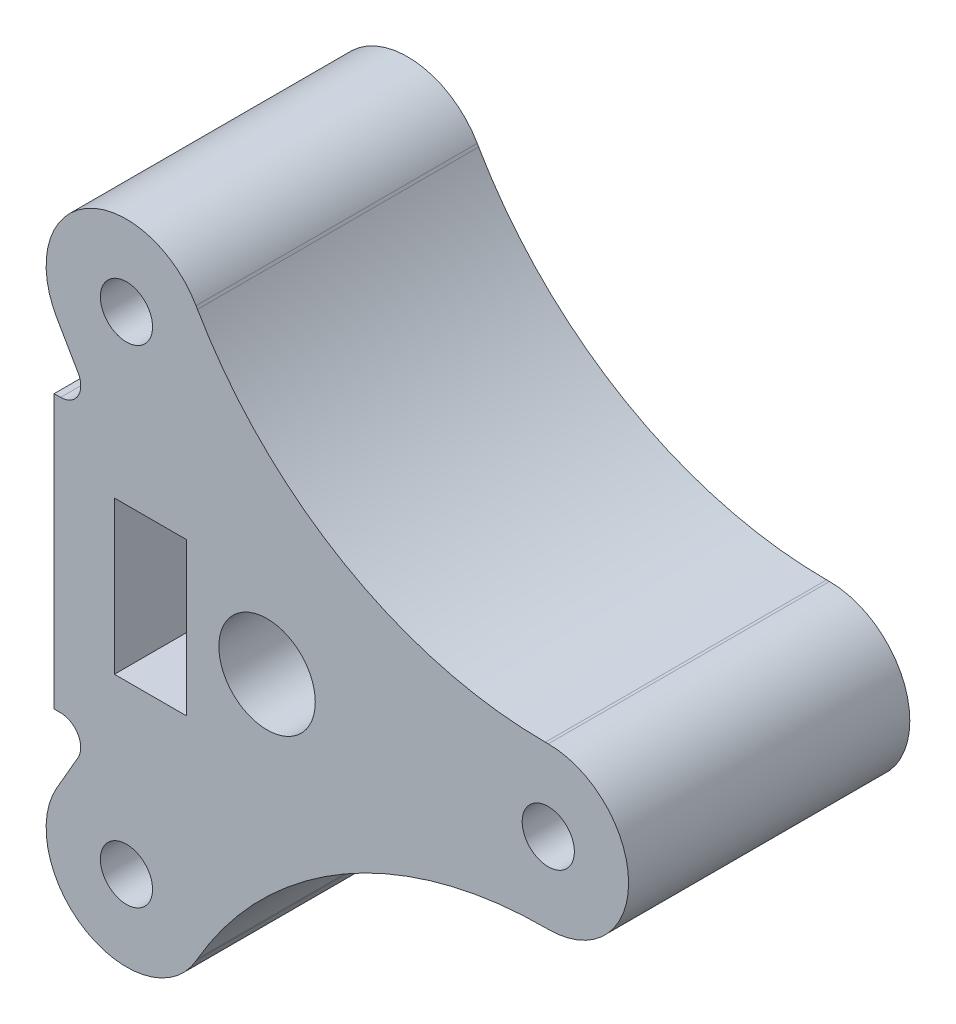
SolidWorks part; units mm, degrees
ref_plane "Front Plane" through (0, 0, 0) normal (0, 0, 1) x (1, 0, 0)
ref_plane "Top Plane" through (0, 0, 0) normal (0, 1, 0) x (1, 0, 0)
ref_plane "Right Plane" through (0, 0, 0) normal (1, 0, 0) x (0, 0, -1)
sketch "Sketch1" plane through (0, 0, 0) normal (0, 0, 1) x (1, 0, 0)
  line L0 (-13.462, 8.636) -> (-1.27, 8.636)
  line L1 (-9.652, 4.826) -> (-5.08, 4.826)
  line L2 (-9.652, 4.826) -> (-9.652, -4.826)
  line L3 (-9.652, -4.826) -> (-5.08, -4.826)
  line L4 (-5.08, 4.826) -> (-5.08, -4.826)
  line L6 (-13.462, -8.636) -> (-1.27, -8.636)
  line L7 (-13.462, 8.636) -> (-13.462, -8.636)
  line L8 (-1.27, 8.636) -> (3.7294, 4.3304)
  line L9 (-1.27, -8.636) -> (3.7294, -4.3304)
  line L10 (-1.27, 8.636) -> (-1.27, -8.636) construction
  circle A0 centre (0, 0) radius 3.048
  arc A1 (3.7294, -4.3304) -> (3.7294, 4.3304) centre (0, 0) ccw
  dimension "D1" = 6.096
  dimension "D2" = 11.43
  dimension "D6" = 5.08
  dimension "D3" = 9.652
  dimension "D4" = 4.572
  dimension "D5" = 4.826
  dimension "D7" = 3.81
extrude "Boss-Extrude1" add sketch "Sketch1" along normal blind 17.78
sketch "Sketch4" plane through (0, 0, 0) normal (0, 0, -1) x (-1, 0, 0)
  circle A0 centre (0, 0) radius 28.575 construction
  dimension "D1" = 57.15
sketch "Sketch3" plane through (-5.08, 0, 0) normal (-1, 0, 0) x (0, 0, 1)
  line L0 (17.78, 4.826) -> (0, 4.826) construction
  line L1 (3.937, -4.826) -> (13.843, -4.826)
  line L2 (3.937, -4.826) -> (3.937, 4.826)
  line L3 (3.937, 4.826) -> (13.843, 4.826)
  line L4 (13.843, -4.826) -> (13.843, 4.826)
  line L5 (3.937, -4.826) -> (13.843, 4.826) construction
  line L6 (3.937, 4.826) -> (13.843, -4.826) construction
  line L8 (3.937, 4.826) -> (0, 4.826)
  line L9 (3.937, 4.826) -> (3.937, -4.826)
  line L10 (3.937, -4.826) -> (0, -4.826)
  line L11 (0, 4.826) -> (0, -4.826)
  point P0 (8.89, 0)
  line M4 (0, 4.826) -> (0, -4.826)
  line M5 (0, -4.826) -> (17.78, -4.826)
  line M7 (17.78, 4.826) -> (0, 4.826)
  dimension "D1" = 9.906
extrude "Boss-Extrude2" add sketch "Sketch3" along normal up to surface (4.572 mm away) contours L2 M5 M7 M4 region at (-5.08, 0, 1.9685) up to face at (-9.652, 0, 8.89)
sketch "Sketch5" plane through (0, 0, 0) normal (0, 0, -1) x (-1, 0, 0)
  line L0 (0, 0) -> (8.89, 15.3979) construction
  line L1 (-2.9329, 5.08) -> (4.4906, 17.9379)
  line L2 (8.6522, 4.826) -> (13.2894, 12.8579)
  line L3 (-2.9329, -5.08) -> (4.4906, -17.9379)
  line L4 (8.6522, -4.826) -> (13.2894, -12.8579)
  line L5 (0, 0) -> (8.89, -15.3979) construction
  line L6 (-2.9329, 5.08) -> (-17.78, 5.08)
  line L7 (-2.9329, -5.08) -> (-17.78, -5.08)
  line L8 (0, 0) -> (-17.78, 0) construction
  line L9 (0, 0) -> (-28.575, 0) construction
  line L11 (8.6522, 4.826) -> (5.08, 4.826)
  line L13 (8.6522, -4.826) -> (5.08, -4.826)
  line L14 (5.08, 4.826) -> (5.08, -4.826)
  arc A1 (13.2894, 12.8579) -> (4.4906, 17.9379) centre (8.89, 15.3979) ccw
  circle A2 centre (8.89, 15.3979) radius 1.651
  arc A4 (4.4906, -17.9379) -> (13.2894, -12.8579) centre (8.89, -15.3979) ccw
  circle A5 centre (8.89, -15.3979) radius 1.651
  arc A7 (-17.78, 5.08) -> (-17.78, -5.08) centre (-17.78, 0) ccw
  circle A8 centre (-17.78, 0) radius 1.651
  circle A9 centre (0, 0) radius 28.575 construction
  circle A12 centre (0, 0) radius 3.048
  point P3 (4.445, 7.699)
  point P13 (4.445, -7.699)
  point P21 (-8.89, 0)
  point P28 (0, 0)
  dimension "D2" = 5.08
  dimension "D3" = 3.302
  dimension "D1" = 17.78
  dimension "D5" = 0
  dimension "D4" = 3
extrude "Boss-Extrude3" add sketch "Sketch5" against normal blind 17.78
fillet "Fillet1" radius 25.4 2 edges at (2.9329, -5.08, 8.89) (2.9329, 5.08, 8.89)
fillet "Fillet2" radius 1.27 2 edges at (-10.8519, 8.636, 8.89) (-10.8519, -8.636, 8.89)
sketch "Sketch2" plane through (-13.462, 0, 0) normal (-1, 0, 0) x (0, 0, 1)
  line L0 (0, 0) -> (17.78, 0) construction
  line L1 (0, 8.636) -> (0, -8.636) construction
  line L2 (17.78, 8.636) -> (17.78, -8.636) construction
  circle A0 centre (8.89, 0) radius 2.794
  dimension "D1" = 5.588
extrude "Cut-Extrude2" cut sketch "Sketch2" against normal blind 12.7
